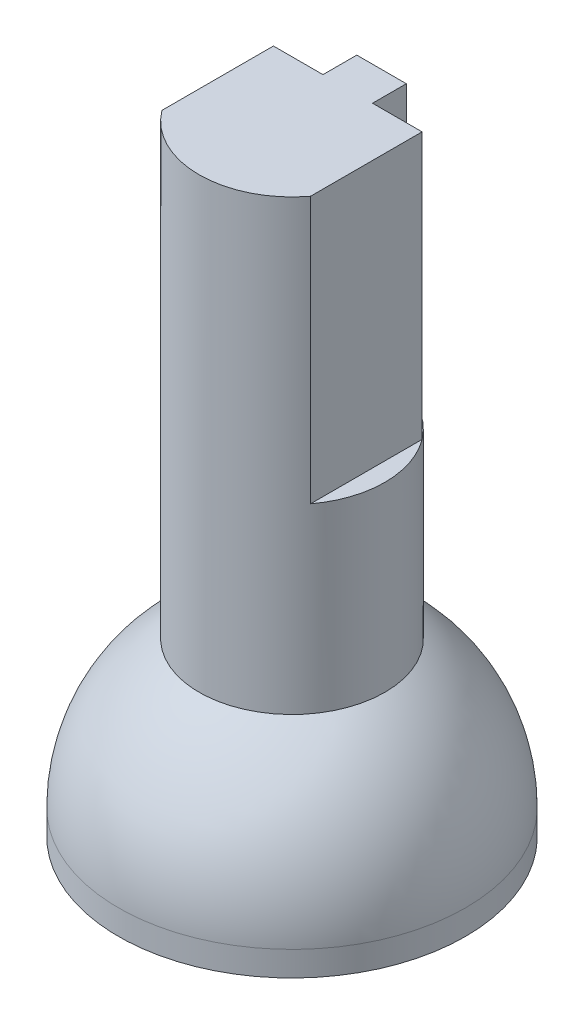
SolidWorks part; units mm, degrees
ref_plane "Front Plane" through (0, 0, 0) normal (0, 0, 1) x (1, 0, 0)
ref_plane "Top Plane" through (0, 0, 0) normal (0, 1, 0) x (1, 0, 0)
ref_plane "Right Plane" through (0, 0, 0) normal (1, 0, 0) x (0, 0, -1)
sketch "Sketch3" plane through (0, 0, 0) normal (0, 0, 1) x (1, 0, 0)
  line L0 (0, 0) -> (0, 12.192) construction
  line L2 (-1.905, 12.192) -> (-1.905, 3.0027)
  line L3 (-3.556, 0) -> (-2.54, 0)
  line L4 (0, 0) -> (-4.2652, 0) construction
  line L7 (-1.27, 2.1997) -> (0, 2.9329)
  line L8 (-1.27, 2.1997) -> (-1.27, 3.6416) construction
  line L9 (-1.905, 12.192) -> (0, 12.192)
  line L11 (0, 12.192) -> (0, 2.9329)
  line L12 (-3.5195, 0.508) -> (-2.4887, 0.508)
  line L13 (-3.556, 0) -> (-3.556, -0.508)
  line L17 (-3.556, -0.508) -> (-3.2262, -0.508)
  line L18 (-2.1997, 1.27) -> (-3.6759, -1.2869) construction
  line L19 (-3.2262, -0.508) -> (-2.1997, 1.27)
  arc A2 (-1.905, 3.0027) -> (-3.556, 0) centre (0, 0) ccw
  arc A5 (-2.54, 0) -> (-1.27, 2.1997) centre (0, 0) cw
  circle A6 centre (0, 0) radius 2.54 construction
  dimension "D1" = 2.54
  dimension "D2" = 12.192
  dimension "D3" = 1.905
  dimension "D5" = 1.016
  dimension "D4" = 60
  dimension "D6" = 0.508
  dimension "D8" = 0.508
revolve "Revolve1" add sketch "Sketch3" angle 360 about L11 region at (-1.1449, 6.6719, 0) region at (-3.1604, 0.2684, 0) region at (-3.3103, -0.2279, 0)
sketch "Sketch4" plane through (0, 12.192, 0) normal (0, 1, 0) x (1, 0, 0)
  line L0 (0, -1.905) -> (0, 1.905) construction
  line L1 (3.1721, -1.905) -> (1.524, -1.905)
  line L2 (-3.1721, 1.905) -> (-1.524, 1.905)
  line L3 (-3.1721, 1.905) -> (-3.1721, -1.905)
  line L4 (-3.1721, -1.905) -> (-1.524, -1.905)
  line L5 (-1.524, 1.905) -> (-1.524, -1.905)
  line L6 (3.1721, 1.905) -> (3.1721, -1.905)
  line L7 (3.1721, 1.905) -> (1.524, 1.905)
  line L8 (1.524, 1.905) -> (1.524, -1.905)
  line L10 (-0.508, 1.836) -> (0.508, 1.836)
  line L11 (-0.508, 1.836) -> (-0.508, 1.143)
  line L12 (-0.508, 1.143) -> (0.508, 1.143)
  line L13 (0.508, 1.836) -> (0.508, 1.143)
  line L14 (-0.508, 1.836) -> (0.508, 1.143) construction
  line L15 (-0.508, 1.143) -> (0.508, 1.836) construction
  line L16 (-0.508, 1.143) -> (-1.524, 1.143)
  line L17 (-0.508, 1.143) -> (-0.508, 1.905)
  line L18 (-0.508, 1.905) -> (-1.524, 1.905)
  line L19 (-1.524, 1.143) -> (-1.524, 1.905)
  line L20 (0.508, 1.143) -> (1.524, 1.143)
  line L21 (0.508, 1.143) -> (0.508, 1.905)
  line L22 (0.508, 1.905) -> (1.524, 1.905)
  line L23 (1.524, 1.143) -> (1.524, 1.905)
  line L24 (-1.524, 3.0703) -> (1.524, 3.0703)
  line L25 (-1.524, 3.0703) -> (-1.524, 1.836)
  line L26 (-1.524, 1.836) -> (1.524, 1.836)
  line L27 (1.524, 3.0703) -> (1.524, 1.836)
  circle A0 centre (0, 0) radius 1.905 construction
  circle A1 centre (0, 0) radius 1.905 construction
  point P15 (0, 1.4895)
  circle M7 centre (0, 0) radius 1.905
  dimension "D1" = 3.048
  dimension "D2" = 1.016
extrude "Cut-Extrude1" cut sketch "Sketch4" against normal blind 5.461 contours L5 L2 L3 L4 L19 M7 | L16 L11 L5 M7 | L26 L19 M7 | L27 L24 L25 L18 L17 L21 L22 M7 | L5 L26 L17 L18 | L10 M7 | L21 L26 L8 L22 | L26 L23 M7 | L13 L20 L8 M7 | L7 L8 L23 L1 L6 M7 | L8 M7 | L5 M7 region at (2.418, 12.192, 0) region at (1.6778, 12.192, 0) region at (1.016, 12.192, -1.8705) region at (0, 12.192, -2.4837) region at (1.2312, 12.192, -1.6307) region at (0.8837, 12.192, -1.4028) region at (-1.6778, 12.192, 0) region at (-2.418, 12.192, 0) region at (0, 12.192, -1.8637) region at (-0.8837, 12.192, -1.4028) region at (-1.2312, 12.192, -1.6307) region at (-1.016, 12.192, -1.8705)
